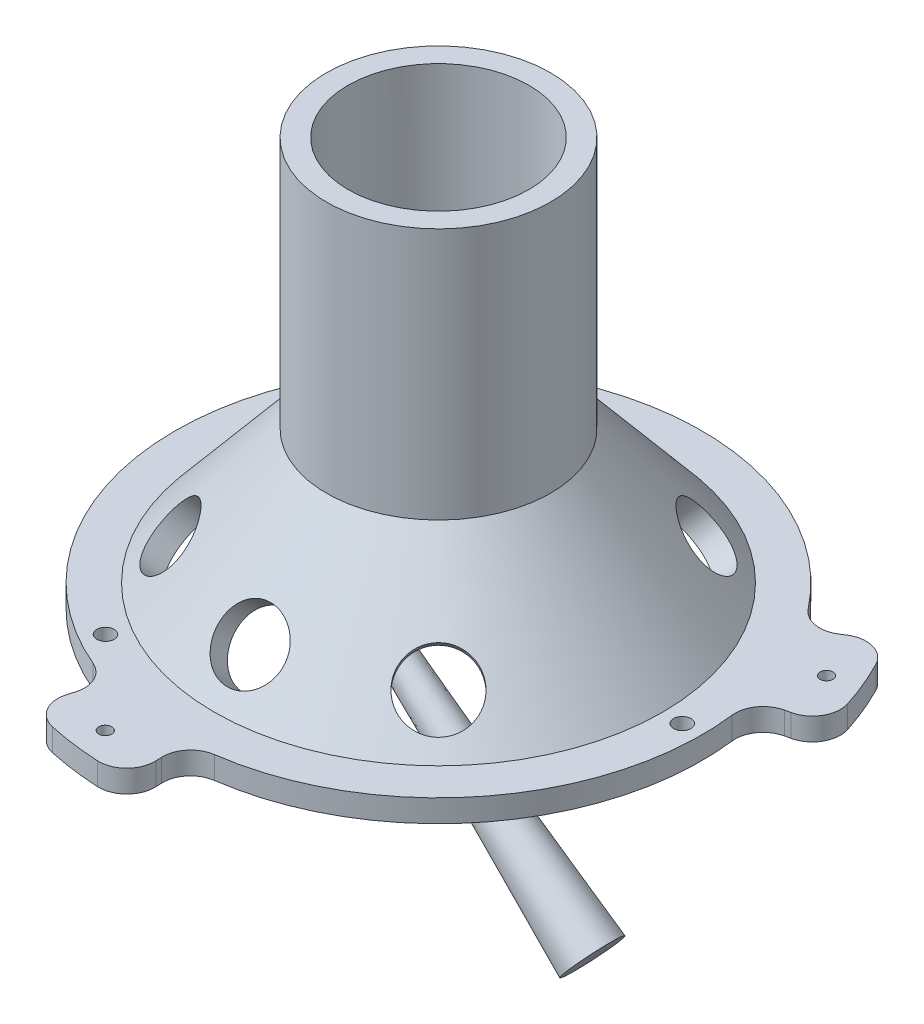
SolidWorks part; units mm, degrees
material "AISI 316 Tôle d'acier inoxydable (SS)"
ref_plane "Front Plane" through (0, 0, 0) normal (0, 0, 1) x (1, 0, 0)
ref_plane "Top Plane" through (0, 0, 0) normal (0, 1, 0) x (1, 0, 0)
ref_plane "Right Plane" through (0, 0, 0) normal (1, 0, 0) x (0, 0, -1)
sketch "Esquisse1" plane through (0, 0, 0) normal (0, 0, 1) x (1, 0, 0)
  line L2 (-47, -19.8351) -> (-47, -23.8351)
  line L3 (-38.1348, -23.8351) -> (-18.1348, 0)
  line L4 (-47, -23.8351) -> (0, -23.8351) construction
  line L5 (0, -23.8351) -> (0, 0) construction
  line L6 (-20, 4) -> (0, 4)
  line L7 (-18.1348, 0) -> (0, 0)
  line L9 (0, 0) -> (0, 4)
  line L10 (-47, -23.8351) -> (-38.1348, -23.8351)
  line L11 (-47, -19.8351) -> (-40, -19.8351)
  line L12 (-40, -19.8351) -> (-20, 4)
  line L13 (-30, -7.9175) -> (-26.9358, -10.4887) construction
  point P14 (-38.1348, -23.8351)
  point P25 (-47, -19.8351)
  dimension "D1" = 47
  dimension "D2" = 50
  dimension "D3" = 4
  dimension "D4" = 7
  dimension "D5" = 20
revolve "Révolution2" add sketch "Esquisse1" angle 360 about L9
sketch "Esquisse3" plane through (0, 0, 0) normal (0, 0, 1) x (1, 0, 0)
  line L0 (-20, 4) -> (-40, -19.8351) construction
  line L2 (-47, -23.8351) -> (47, -23.8351) construction
  line L3 (-38.1348, -23.8351) -> (-18.1348, 0) construction
  line L4 (-18.1348, 0) -> (18.1348, 0) construction
  line L5 (-34.5923, -11.8347) -> (-30.7355, -7.2384)
  line L6 (-30.7355, -7.2384) -> (-10.9564, -23.8351)
  line L7 (-10.9564, -23.8351) -> (-14.8131, -28.4313)
  line L8 (-34.5923, -11.8347) -> (-14.8131, -28.4313)
  dimension "D1" = 6
  dimension "D2" = 1
  dimension "D3" = 9.6047
revolve "Enlèvement de matière-Révolution1" cut sketch "Esquisse3" angle 360 about L8
pattern_circular "Répétition circulaire1" count 4 every 45 about axis through (0, 4, 0) along (0, -1, 0) of "Enlèvement de matière-Révolution1" other way count 4
sketch "Esquisse4" plane through (0, 4, 0) normal (0, 1, 0) x (1, 0, 0)
  circle A0 centre (0, 0) radius 20
extrude "Boss.-Extru.1" add sketch "Esquisse4" along normal blind 45
sketch "Esquisse5" plane through (0, 49, 0) normal (0, 1, 0) x (1, 0, 0)
  line L1 (0, -13) -> (0, 13) construction
  circle A0 centre (0, 0) radius 5.9
  circle A1 centre (0, 0) radius 38.5 construction
  point P0 (0, 0)
  point P5 (0, 13)
  point P7 (0, -13)
  point P15 (0, 0)
  point P19 (0, 0)
  dimension "D1" = 11.8
  dimension "D2" = 13
  dimension "D5" = 77
  dimension "D6" = 77
extrude "Enlèv. mat.-Extru.1" cut sketch "Esquisse5" against normal up to next
sketch "Esquisse6" plane through (0, 0, 0) normal (0, -1, 0) x (-1, 0, 0)
  circle A0 centre (0, 0) radius 16.1348
  circle A1 centre (0, 0) radius 18.1348 construction
  dimension "D1" = 2
extrude "Enlèv. mat.-Extru.2" cut sketch "Esquisse6" against normal up to next
sketch "Esquisse7" plane through (0, 0, 0) normal (0, 0, 1) x (1, 0, 0)
  line L0 (-20, 4) -> (-29.9695, -7.8812) construction
  line L1 (-29.9695, -7.8812) -> (-24.9848, -1.9406) construction
  line L2 (-24.9848, -1.9406) -> (51.6197, -66.2194) construction
  dimension "D1" = 100
ref_plane "Plan1" through (-13.7061, 11.5008, 0) normal (0.766, -0.6428, 0) x (0, 0, -1)
sketch "Esquisse8" plane through (-13.7061, 11.5008, 0) normal (0.766, -0.6428, 0) x (0, 0, -1)
  circle A0 centre (0, -31.3014) radius 2.5
ref_plane "Plan2" through (47.5775, -39.9222, 0) normal (0.766, -0.6428, 0) x (0, 0, -1)
sketch "Esquisse9" plane through (47.5775, -39.9222, 0) normal (0.766, -0.6428, 0) x (0, 0, -1)
  circle A0 centre (0, -31.3014) radius 4.9
loft "Lissage1" add profiles "Esquisse9", "Esquisse8" connector at (27.1806, -64.2302, -4.8811) connector at (-32.2458, -10.594, -0.453)
sketch "Esquisse13" plane through (0, -19.8351, 0) normal (0, 1, 0) x (1, 0, 0)
  line L0 (0, 0) -> (58, 0) construction
  line L1 (0, 0) -> (62.6766, 25.9615) construction
  circle A0 centre (0, 0) radius 58
  circle A1 centre (48.9656, 20.2822) radius 1.15
  circle A2 centre (0, 0) radius 53
  circle A3 centre (-6.9179, -52.5466) radius 1.15
  circle A4 centre (-42.0477, 32.2644) radius 1.15
  point P15 (0, 0)
  circle M3 centre (0, 0) radius 47
  dimension "D1" = 116
  dimension "D3" = 2.3
  dimension "D4" = 106
  dimension "D2" = 22.5
  dimension "D5" = 3
extrude "Boss.-Extru.4" add sketch "Esquisse13" against normal blind 4 contours A4 A2 A3 A1 M3 | A0 A4 A2 A1 A3 region at (-56.3595, -19.8351, 0) region at (46.5182, -19.8351, -19.2685)
sketch "Esquisse14" plane through (0, -19.8351, 0) normal (0, 1, 0) x (1, 0, 0)
  line L0 (0, 0) -> (-51.8901, 27.0123)
  line L1 (0, 0) -> (-39.522, 43.1307)
  line L2 (0, 0) -> (-42.0477, 32.2644) construction
  line L3 (0, 0) -> (57.1133, 12.6617)
  line L4 (0, 0) -> (49.3384, 31.432)
  line L5 (0, 0) -> (-17.5913, -55.7924)
  line L6 (0, 0) -> (2.5517, -58.4443)
  circle A0 centre (0, 0) radius 47
  circle A1 centre (0, 0) radius 58.5
  circle A2 centre (0, 0) radius 58.5
  circle A3 centre (0, 0) radius 58.5
  point P17 (0, 0)
  circle M8 centre (0, 0) radius 58
  dimension "D1" = 94
  dimension "D2" = 10
  dimension "D4" = 117
  dimension "D3" = 10
  dimension "D5" = 3
extrude "Enlèv. mat.-Extru.4" cut sketch "Esquisse14" against normal up to next (4 mm away) contours A0 L4 L1 M8 | A0 L6 L3 M8 | A0 L0 L5 M8 region at (-44.2823, -19.8351, 18.3423) region at (-34.7755, -19.8351, -39.342) region at (51.4503, -19.8351, -10.4844)
fillet "Congé1" radius 5 12 edges at (39.6394, -21.8351, -25.2531) (48.9167, -21.8351, -31.1634) (45.8859, -21.8351, -10.1727) (56.6252, -21.8351, -12.5535) (2.0501, -21.8351, 46.9553) (2.5299, -21.8351, 57.9448) (-17.4409, -21.8351, 55.3156) (-14.1332, -21.8351, 44.8247) (-41.6895, -21.8351, -21.7022) (-51.4466, -21.8351, -26.7814) (-31.7527, -21.8351, -34.652) (-39.1842, -21.8351, -42.7621)
sketch "Esquisse15" plane through (0, -19.8351, 0) normal (0, 1, 0) x (1, 0, 0)
  line L0 (0, 0) -> (47, 0) construction
  arc A0 (6.5555, -46.5406) -> (46.6514, 5.7134) centre (0, 0) ccw construction
  circle A1 centre (43.5, 0) radius 1.55
  circle A2 centre (0, 0) radius 43.5
  circle A3 centre (-21.75, -37.6721) radius 1.55
  circle A4 centre (-21.75, 37.6721) radius 1.55
  point P16 (0, 0)
  dimension "D1" = 3.1
  dimension "D2" = 87
  dimension "D3" = 3
extrude "Enlèv. mat.-Extru.5" cut sketch "Esquisse15" against normal up to next (4 mm away) contours L0 A1 A2 | L0 A2 A1 | A2 L0 A1 | A1 L0 A2 | A2 A4 | A2 A4 | A2 A3 | A2 A3 region at (44.1528, -19.8351, -0.6616) region at (42.8372, -19.8351, 0.654) region at (42.8372, -19.8351, -0.654) region at (44.1528, -19.8351, 0.6616) region at (-21.4186, -19.8351, -37.0981) region at (-22.0764, -19.8351, -38.2375) region at (-22.0764, -19.8351, 38.2375) region at (-21.4186, -19.8351, 37.0981)
